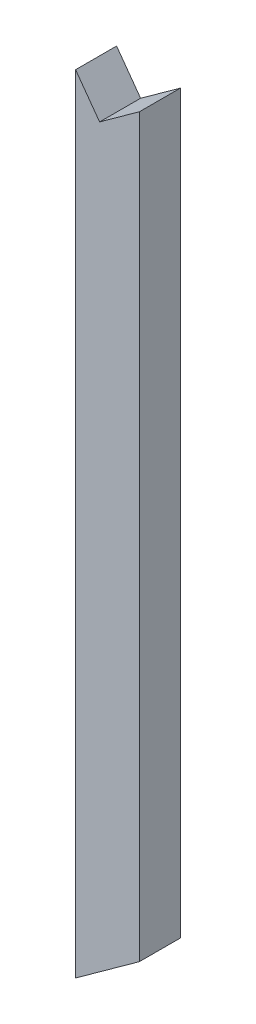
SolidWorks part; units mm, degrees
ref_plane "Front Plane" through (0, 0, 0) normal (0, 0, 1) x (1, 0, 0)
ref_plane "Top Plane" through (0, 0, 0) normal (0, 1, 0) x (1, 0, 0)
ref_plane "Right Plane" through (0, 0, 0) normal (1, 0, 0) x (0, 0, -1)
sketch "Sketch1" plane through (0, 0, 0) normal (0, 1, 0) x (1, 0, 0)
  line L1 (-35, 22.5) -> (35, 22.5)
  line L2 (-35, 22.5) -> (-35, -22.5)
  line L3 (-35, -22.5) -> (35, -22.5)
  line L4 (35, 22.5) -> (35, -22.5)
  line L5 (-35, 22.5) -> (35, -22.5) construction
  line L6 (-35, -22.5) -> (35, 22.5) construction
  point P0 (0, 0)
  dimension "D1" = 45
  dimension "D2" = 70
extrude "Shape" add sketch "Sketch1" along normal blind 1000
sketch "Sketch2" [suppressed] plane through (0, 0, 22.5) normal (0, 0, 1) x (1, 0, 0)
  line L0 (-35, 400) -> (35, 330)
  line L1 (35, 400) -> (35, 0) construction
  line L2 (-35, 400) -> (35, 400) construction
  line L3 (35, 200) -> (-35, 200) construction
  line L4 (-35, 0) -> (35, 70)
  line L7 (-35, 0) -> (35, 0)
  line L8 (35, 0) -> (35, 400)
  line L9 (35, 400) -> (-35, 400)
  line L10 (-35, 400) -> (-35, 0)
  line L11 (-35, 0) -> (35, 0)
  line L12 (35, 0) -> (35, 400)
  line L13 (35, 400) -> (-35, 400)
  line L14 (-35, 400) -> (-35, 0)
  line M7 (-35, 0) -> (35, 0)
  line M8 (35, 0) -> (35, 400)
  line M9 (35, 400) -> (-35, 400)
  dimension "D1" = 45
  dimension "D2" = 0
extrude "Merger cut" [suppressed] cut sketch "Sketch2" against normal up to next contours L0 M9 M8 | L4 M7 M8
sketch "Sketch3" plane through (0, 0, 22.5) normal (0, 0, 1) x (1, 0, 0)
  line L0 (149.47, 940.7422) -> (-8.672, 826.654) construction
  line L1 (149.47, 940.7422) -> (-8.672, 826.654)
  line L2 (-35, 863.1483) -> (123.142, 977.2365) construction
  line L3 (-35, 863.1483) -> (123.142, 977.2365)
  line L4 (-8.672, 826.654) -> (751.9158, -227.626) construction
  line L5 (-8.672, 826.654) -> (751.9158, -227.626)
  line L6 (-8.672, 826.654) -> (-35, 863.1483) construction
  line L7 (-8.672, 826.654) -> (-35, 863.1483)
  line L8 (775.9846, 585.0675) -> (-35, 0) construction
  line L9 (775.9846, 585.0675) -> (-35, 0)
  line L10 (-35, 0) -> (35, 0)
  line L11 (35, 0) -> (35, 1000)
  line L12 (35, 1000) -> (-35, 1000)
  line L13 (-35, 1000) -> (-35, 0)
  line L14 (-35, 0) -> (35, 0)
  line L15 (35, 0) -> (35, 1000)
  line L16 (35, 1000) -> (-35, 1000)
  line L17 (-35, 1000) -> (-35, 0)
  line M5 (-35, 0) -> (35, 0)
  line M6 (35, 0) -> (35, 1000)
  line M7 (35, 1000) -> (-35, 1000)
  line M8 (-35, 1000) -> (-35, 0)
  dimension "D1" = 0
extrude "Front diagonal cut" cut sketch "Sketch3" against normal up to next contours L3 M8 M6 M7 | L7 L1 L3 M6 | L9 M6 M5 region at (6.0738, 867.1781, 22.5) region at (-2.6396, 943.247, 22.5) region at (11.6667, 16.8333, 22.5)
